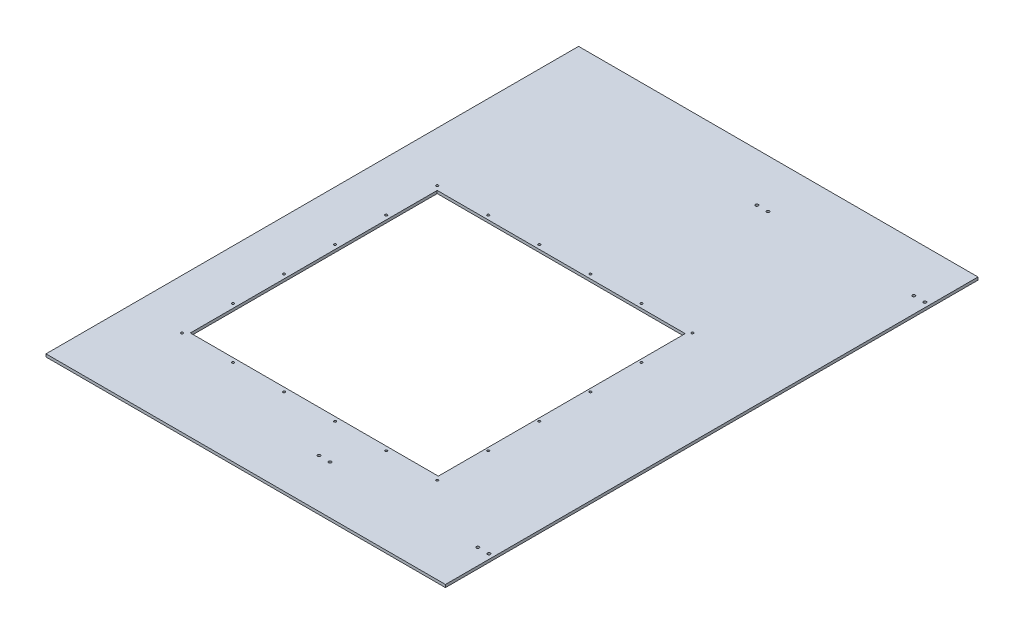
SolidWorks part; units mm, degrees
ref_plane "Front Plane" through (0, 0, 0) normal (0, 0, 1) x (1, 0, 0)
ref_plane "Top Plane" through (0, 0, 0) normal (0, 1, 0) x (1, 0, 0)
ref_plane "Right Plane" through (0, 0, 0) normal (1, 0, 0) x (0, 0, -1)
sketch "Sketch1" plane through (0, 0, 0) normal (0, 1, 0) x (1, 0, 0)
  line L1 (-457.2, -609.6) -> (457.2, -609.6)
  line L2 (-457.2, -609.6) -> (-457.2, 609.6)
  line L3 (-457.2, 609.6) -> (457.2, 609.6)
  line L4 (457.2, -609.6) -> (457.2, 609.6)
  line L5 (-457.2, -609.6) -> (457.2, 609.6) construction
  line L6 (-457.2, 609.6) -> (457.2, -609.6) construction
  point P0 (0, 0)
  dimension "D1" = 1219.2
  dimension "D2" = 914.4
extrude "Boss-Extrude1" add sketch "Sketch1" along normal blind 6.35
sketch "Sketch2" plane through (0, 0, 0) normal (0, -1, 0) x (1, 0, 0)
  line L0 (457.2, 609.6) -> (457.2, -609.6) construction
  circle A4 centre (56.9595, 498.8814) radius 3.2639
  circle A5 centre (82.3595, 498.8814) radius 3.2639
  circle A6 centre (446.0875, 498.8814) radius 3.2639
  circle A7 centre (420.6875, 498.8814) radius 3.2639
  circle A12 centre (61.722, -498.8814) radius 3.2639
  circle A13 centre (87.122, -498.8814) radius 3.2639
  circle A14 centre (420.878, -498.8814) radius 3.2639
  circle A15 centre (446.278, -498.8814) radius 3.2639
  dimension "D1" = 6.5278
  dimension "D2" = 10.922
  dimension "D3" = 11.1125
  dimension "D4" = 36.322
  dimension "D5" = 36.5125
  dimension "D6" = 370.078
  dimension "D7" = 374.8405
  dimension "D8" = 395.478
  dimension "D9" = 400.2405
  dimension "D10" = 110.7186
  dimension "D11" = 1108.4814
extrude "Cut-Extrude1" cut sketch "Sketch2" against normal through all
sketch "Sketch3" plane through (0, 6.35, 0) normal (0, 1, 0) x (1, 0, 0)
  line L4 (-333.375, 162.179) -> (-333.375, -402.971)
  line L13 (-342.9, 171.704) -> (243.8908, 171.704) construction
  line L14 (-342.9, 171.704) -> (-342.9, -412.496) construction
  line L15 (-342.9, -412.496) -> (243.8908, -412.496) construction
  line L16 (243.8908, 171.704) -> (243.8908, -412.496) construction
  line L18 (-333.375, -402.971) -> (234.3658, -402.971)
  line L19 (234.3658, 162.179) -> (234.3658, -402.971)
  line L20 (-333.375, 162.179) -> (234.3658, 162.179)
  circle A2 centre (241.3, 171.704) radius 2.5908
  circle A4 centre (241.3, 54.864) radius 2.5908
  circle A6 centre (241.3, -61.976) radius 2.5908
  circle A8 centre (241.3, -178.816) radius 2.5908
  circle A10 centre (241.3, -295.656) radius 2.5908
  circle A12 centre (241.3, -412.496) radius 2.5908
  circle A14 centre (-342.9, -412.496) radius 2.5908
  circle A16 centre (-226.06, -412.496) radius 2.5908
  circle A18 centre (-109.22, -412.496) radius 2.5908
  circle A20 centre (7.62, -412.496) radius 2.5908
  circle A22 centre (124.46, -412.496) radius 2.5908
  circle A24 centre (-342.9, -295.656) radius 2.5908
  circle A26 centre (-342.9, -178.816) radius 2.5908
  circle A28 centre (-342.9, -61.976) radius 2.5908
  circle A30 centre (-342.9, 54.864) radius 2.5908
  circle A32 centre (124.46, 171.704) radius 2.5908
  circle A34 centre (7.62, 171.704) radius 2.5908
  circle A36 centre (-109.22, 171.704) radius 2.5908
  circle A38 centre (-226.06, 171.704) radius 2.5908
  circle A39 centre (446.0875, -498.8814) radius 3.2639 construction
  circle A40 centre (-342.9, 171.704) radius 2.5908
  dimension "D1" = 5.1816
  dimension "D2" = 204.7875
  dimension "D3" = 321.6275
  dimension "D4" = 438.4675
  dimension "D5" = 555.3075
  dimension "D6" = 672.1475
  dimension "D7" = 788.9875
  dimension "D8" = 86.3854
  dimension "D9" = 203.2254
  dimension "D10" = 320.0654
  dimension "D11" = 436.9054
  dimension "D12" = 553.7454
  dimension "D13" = 670.5854
  dimension "D14" = 9.525
extrude "Cut-Extrude2" cut sketch "Sketch3" against normal through all contours L20 L4 L18 L19 | A40 | A38 | A36 | A34 | A32 | A2 | A4 | A6 | A8 | A10 | A12 | A20 | A18 | A16 | A14 | A24 | A26 | A28 | A30 | A22 | L4 L18 L19 L20 region at (-49.5046, 6.35, 120.396) region at (241.3, 6.35, -171.704) region at (241.3, 6.35, -54.864) region at (241.3, 6.35, 61.976) region at (241.3, 6.35, 178.816) region at (241.3, 6.35, 295.656) region at (241.3, 6.35, 412.496) region at (-342.9, 6.35, 412.496) region at (-226.06, 6.35, 412.496) region at (-109.22, 6.35, 412.496) region at (7.62, 6.35, 412.496) region at (124.46, 6.35, 412.496) region at (-342.9, 6.35, 295.656) region at (-342.9, 6.35, 178.816) region at (-342.9, 6.35, 61.976) region at (-342.9, 6.35, -54.864) region at (124.46, 6.35, -171.704) region at (7.62, 6.35, -171.704) region at (-109.22, 6.35, -171.704) region at (-226.06, 6.35, -171.704) region at (-342.9, 6.35, -171.704)
